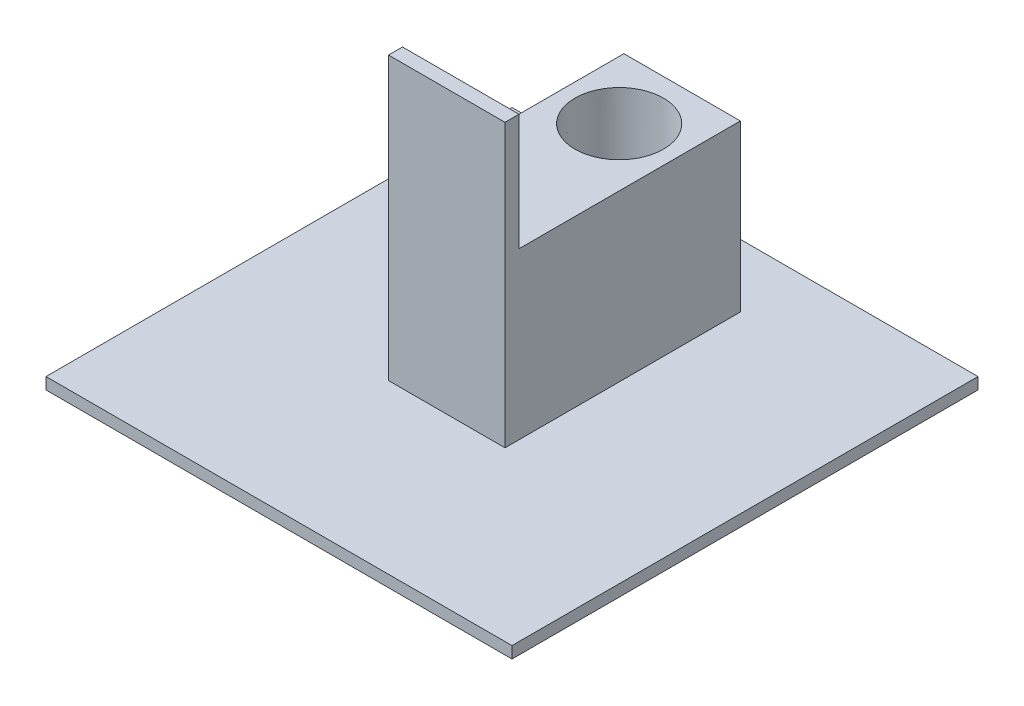
SolidWorks part; units mm, degrees
ref_plane "Front Plane" through (0, 0, 0) normal (0, 0, 1) x (1, 0, 0)
ref_plane "Top Plane" through (0, 0, 0) normal (0, 1, 0) x (1, 0, 0)
ref_plane "Right Plane" through (0, 0, 0) normal (1, 0, 0) x (0, 0, -1)
sketch "Sketch1" plane through (0, 0, 0) normal (0, 1, 0) x (1, 0, 0)
  line L0 (-48.75, 25.7143) -> (51.25, -74.2857) construction
  line L1 (-48.75, 25.7143) -> (51.25, 25.7143)
  line L2 (-48.75, 25.7143) -> (-48.75, -74.2857)
  line L3 (-48.75, -74.2857) -> (51.25, -74.2857)
  line L4 (51.25, 25.7143) -> (51.25, -74.2857)
  line L5 (51.25, 25.7143) -> (-48.75, -74.2857) construction
  dimension "D1" = 100
  dimension "D2" = 100
extrude "Boss-Extrude1" add sketch "Sketch1" along normal blind 38
sketch "Sketch3" plane through (0, 0, 0) normal (0, -1, 0) x (1, 0, 0)
  line L0 (-48.75, 74.2857) -> (51.25, -25.7143) construction
  line L1 (51.25, 74.2857) -> (-48.75, -25.7143) construction
  circle A0 centre (-27.0343, 52.57) radius 3
  circle A1 centre (29.5343, 52.57) radius 3
  circle A2 centre (29.5343, -3.9986) radius 3
  circle A3 centre (-27.0343, -3.9986) radius 3
  point P10 (1.25, 24.2857)
  point P20 (1.25, 24.2857)
  dimension "D1" = 6
  dimension "D2" = 40
  dimension "D3" = 4
extrude "Boss-Extrude2" add sketch "Sketch3" along normal blind 3
sketch "Sketch4" plane through (0, 0, 0) normal (0, -1, 0) x (1, 0, 0)
  line L0 (-48.75, 74.2857) -> (51.25, -25.7143) construction
  line L1 (51.25, 74.2857) -> (-48.75, -25.7143) construction
  line L2 (1.25, 18.7992) -> (1.25, 53.1215) construction
  circle A0 centre (1.25, 1.2857) radius 8.25
  point P8 (1.25, 24.2857)
  dimension "D1" = 16.5
  dimension "D2" = 23
sketch "Sketch5" plane through (0, 38, 0) normal (0, 1, 0) x (1, 0, 0)
  circle A0 centre (1.25, -1.2857) radius 9.5
  dimension "D1" = 19
loft "Cut-Loft1" cut profiles "Sketch4", "Sketch5" connector at (1.25, 0, -6.9643) connector at (0.7475, 38, -8.201)
sketch "Sketch6" plane through (0, 38, 0) normal (0, 1, 0) x (1, 0, 0)
  line L0 (1.25, 6.9643) -> (43.234, 6.9643) construction
  line L5 (-11.25, -35.2857) -> (13.75, -35.2857)
  line L6 (-11.25, -35.2857) -> (-11.25, -38.2857)
  line L7 (-11.25, -38.2857) -> (13.75, -38.2857)
  line L8 (13.75, -35.2857) -> (13.75, -38.2857)
  line L9 (1.25, 6.9643) -> (1.25, -54.9835) construction
  circle A1 centre (1.25, -1.2857) radius 8.25 construction
  dimension "D1" = 34
  dimension "D2" = 3
  dimension "D3" = 25
extrude "Boss-Extrude3" add sketch "Sketch6" along normal blind 25
sketch "Sketch9" plane through (0, 38, 0) normal (0, 1, 0) x (1, 0, 0)
  line L0 (-11.25, -35.2857) -> (-11.25, -38.2857) construction
  line L1 (-49.7997, 27.7514) -> (-11.25, 27.7514)
  line L2 (-49.7997, 27.7514) -> (-49.7997, -78.7385)
  line L3 (-49.7997, -78.7385) -> (-21.6003, -78.7385)
  line L4 (-11.25, 12.2228) -> (-11.25, -38.2857)
  line L5 (53.4069, 27.7514) -> (13.75, 27.7514)
  line L6 (53.4069, 27.7514) -> (53.4069, -79.3424)
  line L7 (53.4069, -79.3424) -> (26.1849, -79.3424)
  line L8 (13.75, 12.2228) -> (13.75, -38.2857)
  line L9 (13.75, -38.2857) -> (13.75, -35.2857) construction
  line L10 (-11.25, -38.2857) -> (13.75, -38.2857) construction
  line L11 (-11.25, -38.2857) -> (13.75, -38.2857)
  line L12 (-21.6003, -78.7385) -> (-21.6003, -84.0383)
  line L13 (-21.6003, -84.0383) -> (26.1849, -84.0383)
  line L14 (26.1849, -79.3424) -> (26.1849, -84.0383)
  line L15 (-11.25, 27.7514) -> (13.75, 27.7514)
  line L16 (-11.25, 12.2228) -> (13.75, 12.2228)
  dimension "D1" = 0
  dimension "D2" = 0
  dimension "D3" = 0
extrude "Cut-Extrude3" cut sketch "Sketch9" against normal blind 35.5
sketch "Sketch10" plane through (0, 0, 0) normal (1, 0, 0) x (0, 0, -1)
  line L0 (-87.5297, 2.5) -> (30.146, 2.5)
  line L1 (-74.2857, 2.5) -> (25.7143, 2.5) construction
  line L2 (-38.2857, 2.5) -> (12.2228, 2.5) construction
  point P6 (-87.5297, 2.5)
split "Split2" trim tools "Sketch10" bodies to split 107 resulting bodies 108 109
